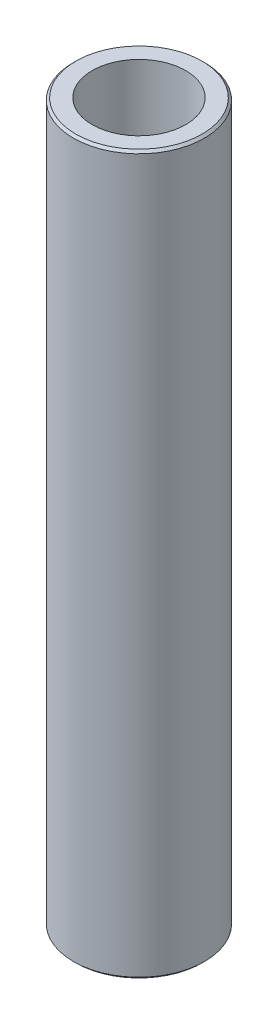
SolidWorks part; units mm, degrees
ref_plane "Front Plane" through (0, 0, 0) normal (0, 0, 1) x (1, 0, 0)
ref_plane "Top Plane" through (0, 0, 0) normal (0, 1, 0) x (1, 0, 0)
ref_plane "Right Plane" through (0, 0, 0) normal (1, 0, 0) x (0, 0, -1)
sketch "Sketch1" plane through (0, 0, 0) normal (0, 1, 0) x (1, 0, 0)
  circle A0 centre (0, 0) radius 52.5
  dimension "SHAFT_OD" = 105
extrude "Boss-Extrude1" add sketch "Sketch1" along normal blind 574.836
sketch "Sketch2" plane through (0, 0, 0) normal (0, 1, 0) x (1, 0, 0)
  circle A0 centre (0, 0) radius 37.4942
  dimension "BORE_D" = 74.9884
extrude "Cut-Extrude1" cut sketch "Sketch2" along normal through all
chamfer "Chamfer1" distance 1.8789 angle 45 2 edges at (0, 574.836, 52.5) (0, 0, 52.5)
